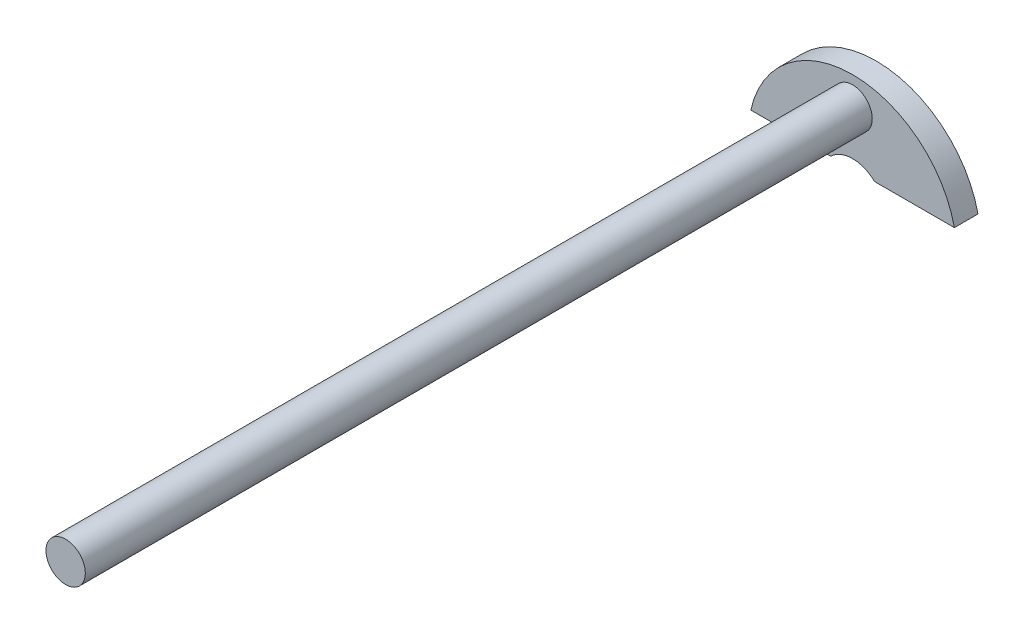
SolidWorks part; units mm, degrees
ref_plane "Front Plane" through (0, 0, 0) normal (0, 0, 1) x (1, 0, 0)
ref_plane "Top Plane" through (0, 0, 0) normal (0, 1, 0) x (1, 0, 0)
ref_plane "Right Plane" through (0, 0, 0) normal (1, 0, 0) x (0, 0, -1)
sketch "Sketch3" plane through (0, 0, 0) normal (0, 0, 1) x (1, 0, 0)
  line L2 (-12.9353, 2.8708) -> (-2.7855, 2.8708)
  line L3 (-12.9373, -2.8615) -> (-2.7949, -2.8615)
  line L4 (2.7855, 2.8708) -> (12.9353, 2.8708)
  line L5 (2.7949, -2.8615) -> (12.9373, -2.8615)
  circle A0 centre (0, 0) radius 13.25
  circle A1 centre (0, 0) radius 15
  arc A2 (-2.7949, -2.8615) -> (2.7949, -2.8615) centre (0, 0) ccw
  arc A3 (2.7855, 2.8708) -> (-2.7855, 2.8708) centre (0, 0) ccw
  dimension "D1" = 26.5
  dimension "D2" = 30
  dimension "D3" = 8
  dimension "D4" = 10.1498
  dimension "D5" = 10.1424
extrude "BasePlate" add sketch "Sketch3" along normal blind 3 contours A3 L4 A0 L2 region at (0, 7.2894, 0)
sketch "Sketch5" plane through (0, 0, 3) normal (0, 0, 1) x (1, 0, 0)
  line L0 (-12.9353, 2.8708) -> (12.9353, 2.8708) construction
  line L1 (0, 2.8708) -> (0, 16.3708) construction
  circle A3 centre (0, 9.6208) radius 2.5
  dimension "D1" = 5
  dimension "D2" = 6.75
extrude "Rod" add sketch "Sketch5" along normal blind 100
